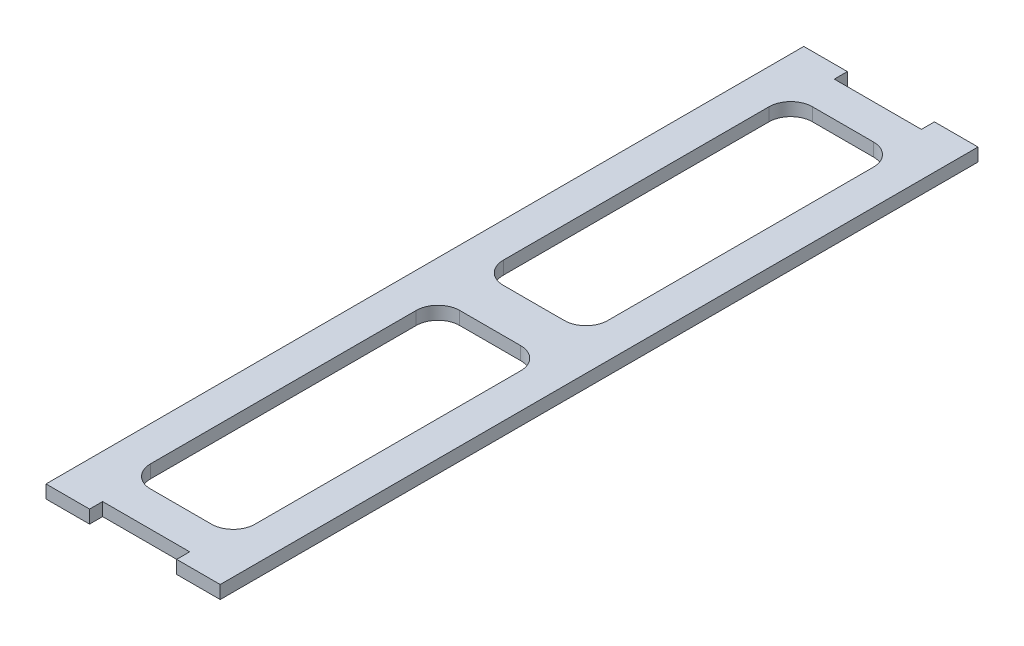
SolidWorks part; units mm, degrees
material "1023 Arkusz stali węglowej (SS)"
ref_plane "Płaszczyzna przednia" through (0, 0, 0) normal (0, 0, 1) x (1, 0, 0)
ref_plane "Płaszczyzna górna" through (0, 0, 0) normal (0, 1, 0) x (1, 0, 0)
ref_plane "Płaszczyzna prawa" through (0, 0, 0) normal (1, 0, 0) x (0, 0, -1)
sketch "Szkic1" plane through (0, 0, 0) normal (0, 1, 0) x (1, 0, 0)
  line L144 (491.5363, 27.1379) -> (491.5363, -59.8621)
  line L145 (491.5363, -59.8621) -> (501.5363, -59.8621)
  line L146 (521.5363, -56.8621) -> (501.5363, -56.8621)
  line L147 (521.5363, -56.8621) -> (521.5363, -59.8621)
  line L148 (521.5363, -59.8621) -> (531.5363, -59.8621)
  line L149 (531.5363, -59.8621) -> (531.5363, 27.1379)
  line L150 (501.5363, -56.8621) -> (501.5363, -59.8621)
  line L151 (499.5363, 17.1379) -> (499.5363, -43.8621)
  line L152 (523.5363, -43.8621) -> (523.5363, 17.1379)
  line L153 (504.5363, 22.1379) -> (518.5363, 22.1379)
  line L154 (518.5363, -48.8621) -> (504.5363, -48.8621)
  line L155 (491.5363, 27.1379) -> (491.5363, 114.1379)
  line L156 (491.5363, 114.1379) -> (501.5363, 114.1379)
  line L157 (521.5363, 111.1379) -> (501.5363, 111.1379)
  line L158 (521.5363, 111.1379) -> (521.5363, 114.1379)
  line L159 (521.5363, 114.1379) -> (531.5363, 114.1379)
  line L160 (531.5363, 114.1379) -> (531.5363, 27.1379)
  line L161 (501.5363, 111.1379) -> (501.5363, 114.1379)
  line L162 (499.5363, 37.1379) -> (499.5363, 98.1379)
  line L163 (523.5363, 98.1379) -> (523.5363, 37.1379)
  line L164 (504.5363, 32.1379) -> (518.5363, 32.1379)
  line L165 (518.5363, 103.1379) -> (504.5363, 103.1379)
  arc A66 (518.5363, -48.8621) -> (523.5363, -43.8621) centre (518.5363, -43.8621) ccw
  arc A67 (504.5363, 22.1379) -> (499.5363, 17.1379) centre (504.5363, 17.1379) ccw
  arc A68 (499.5363, -43.8621) -> (504.5363, -48.8621) centre (504.5363, -43.8621) ccw
  arc A69 (523.5363, 17.1379) -> (518.5363, 22.1379) centre (518.5363, 17.1379) ccw
  arc A70 (523.5363, 98.1379) -> (518.5363, 103.1379) centre (518.5363, 98.1379) ccw
  arc A71 (499.5363, 37.1379) -> (504.5363, 32.1379) centre (504.5363, 37.1379) ccw
  arc A72 (504.5363, 103.1379) -> (499.5363, 98.1379) centre (504.5363, 98.1379) ccw
  arc A73 (518.5363, 32.1379) -> (523.5363, 37.1379) centre (518.5363, 37.1379) ccw
extrude "Dodanie-wyciągnięcie1" add sketch "Szkic1" along normal blind 3
